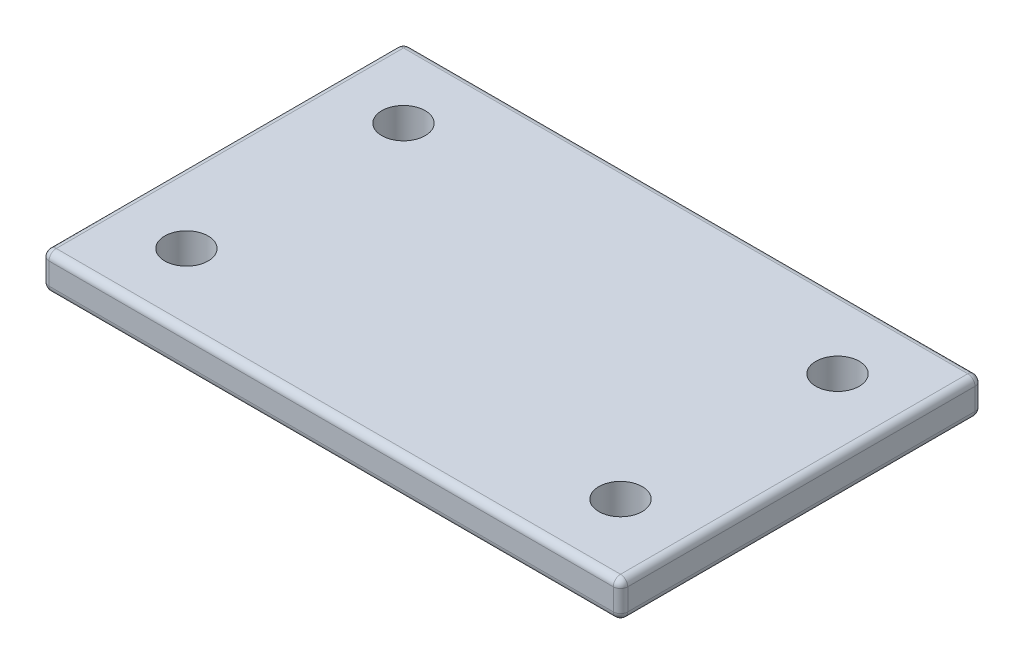
SolidWorks part; units mm, degrees
ref_plane "Front Plane" through (0, 0, 0) normal (0, 0, 1) x (1, 0, 0)
ref_plane "Top Plane" through (0, 0, 0) normal (0, 1, 0) x (1, 0, 0)
ref_plane "Right Plane" through (0, 0, 0) normal (1, 0, 0) x (0, 0, -1)
sketch "Sketch1" plane through (0, 0, 0) normal (0, 1, 0) x (1, 0, 0)
  line L1 (-80, -50) -> (80, -50)
  line L2 (-80, -50) -> (-80, 50)
  line L3 (-80, 50) -> (80, 50)
  line L4 (80, -50) -> (80, 50)
  line L5 (-80, -50) -> (80, 50) construction
  line L6 (-80, 50) -> (80, -50) construction
  point P0 (0, 0)
  dimension "D1" = 160
  dimension "D2" = 100
extrude "Boss-Extrude1" add sketch "Sketch1" along normal blind 10
sketch "Sketch2" plane through (0, 10, 0) normal (0, 1, 0) x (1, 0, 0)
  line L0 (-80, 50) -> (-80, -50) construction
  line L2 (80, 50) -> (-80, 50) construction
  line L3 (-80, -50) -> (80, -50) construction
  line L4 (0, 50) -> (0, -63.1792) construction
  circle A0 centre (-60, 30) radius 6
  circle A1 centre (-60, -30) radius 6
  circle A2 centre (60, -30) radius 6
  circle A3 centre (60, 30) radius 6
  dimension "D1" = 12
  dimension "D2" = 12
  dimension "D3" = 20
  dimension "D4" = 20
  dimension "D5" = 20
  dimension "D6" = 20
extrude "Cut-Extrude1" cut sketch "Sketch2" against normal through all contours A0 | A3 | A2 | A1
fillet "Fillet1" radius 2 4 edges at (80, 10, 0) (0, 10, 50) (-80, 10, 0) (0, 10, -50)
fillet "Fillet2" radius 2 4 edges at (80, 0, 0) (0, 0, -50) (-80, 0, 0) (0, 0, 50)
fillet "Fillet3" radius 2 12 edges at (-79.4142, 9.4142, -49.4142) (-79.4142, 0.5858, -49.4142) (-79.4142, 9.4142, 49.4142) (-79.4142, 0.5858, 49.4142) (79.4142, 9.4142, -49.4142) (79.4142, 0.5858, -49.4142) (79.4142, 9.4142, 49.4142) (79.4142, 0.5858, 49.4142) (-80, 5, -50) (-80, 5, 50) (80, 5, -50) (80, 5, 50)
